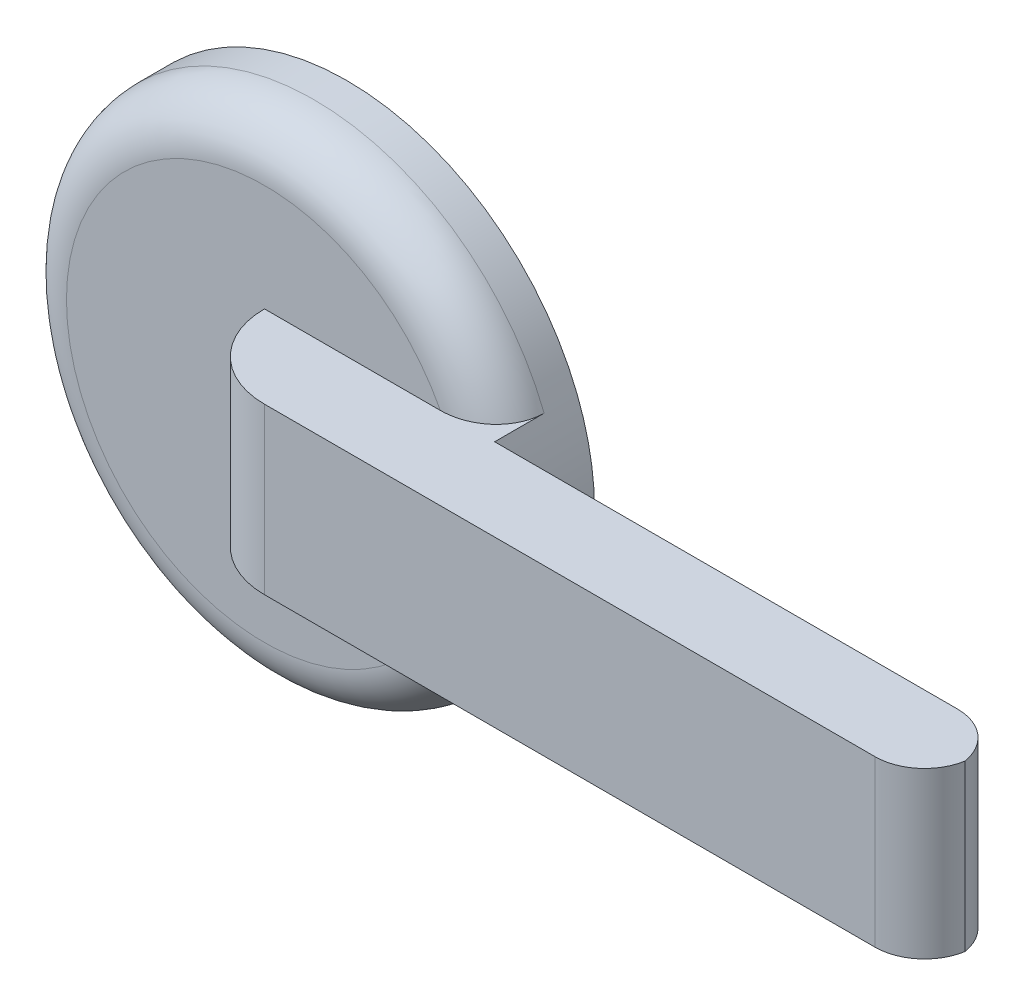
SolidWorks part; units mm, degrees
ref_plane "Front Plane" through (0, 0, 0) normal (0, 0, 1) x (1, 0, 0)
ref_plane "Top Plane" through (0, 0, 0) normal (0, 1, 0) x (1, 0, 0)
ref_plane "Right Plane" through (0, 0, 0) normal (1, 0, 0) x (0, 0, -1)
sketch "Sketch1" plane through (0, 0, 0) normal (0, 0, 1) x (1, 0, 0)
  circle A0 centre (0, 0) radius 38.1
extrude "Boss-Extrude1" add sketch "Sketch1" along normal blind 12.7
sketch "Sketch2" plane through (0, 0, 12.7) normal (0, 0, 1) x (1, 0, 0)
  line L0 (0, -11.3873) -> (114.3, -11.3873)
  line L1 (0, -11.3873) -> (0, 14.0127)
  line L2 (114.3, -11.3873) -> (114.3, 14.0127)
  line L3 (0, 14.0127) -> (114.3, 14.0127)
  line L4 (-38.1, 0) -> (114.3, 0) construction
  circle A0 centre (0, 0) radius 38.1 construction
  dimension "D1" = 152.4
  dimension "D2" = 114.3
  dimension "D3" = 25.4
extrude "Boss-Extrude2" add sketch "Sketch2" along normal blind 12.7
fillet "Fillet1" radius 12.7 1 edges at (0, 1.3127, 25.4)
fillet "Fillet4" radius 7.62 2 edges at (114.3, 1.3127, 12.7) (114.3, 1.3127, 25.4)
fillet "Fillet5" radius 7.62 1 edges at (-38.0745, -1.3925, 12.7)
